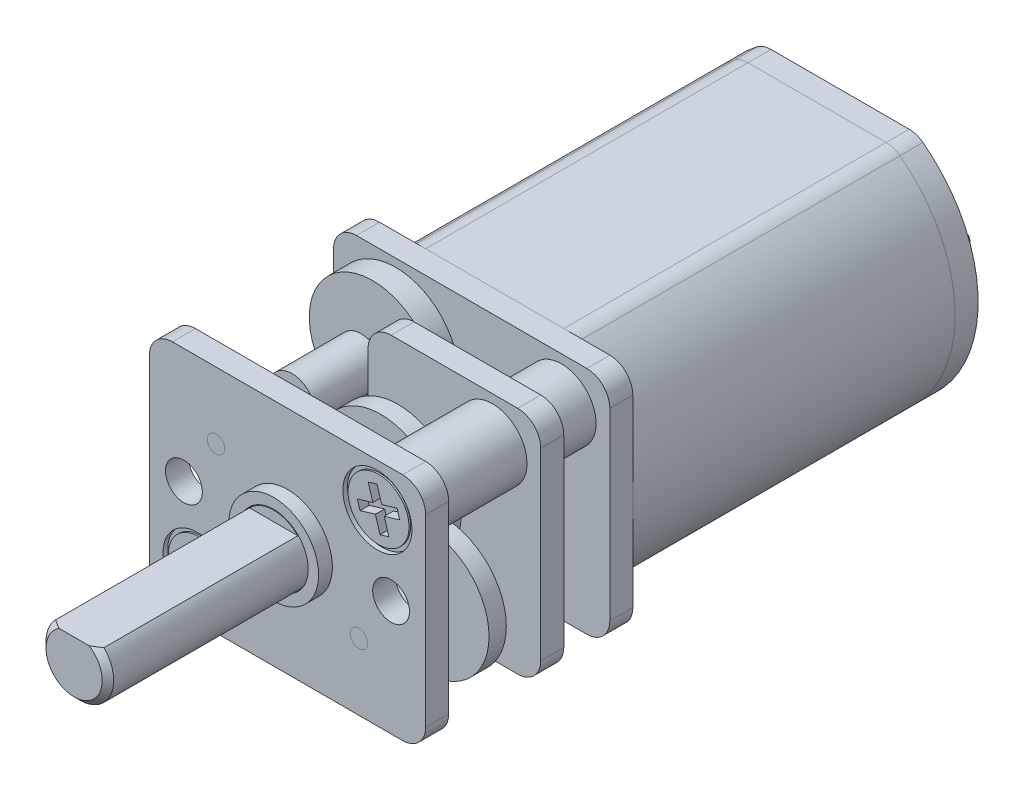
SolidWorks part; units mm, degrees
note: The reader was unsure of these and kept them because the rebuilt part matched: shared geometry of "Sketch2<2>", "Sketch9<3>", "Sketch12<2>", "Sketch29<3>".
material "Plain Carbon Steel"
ref_plane "Front Plane" through (0, 0, 0) normal (0, 0, 1) x (1, 0, 0)
ref_plane "Top Plane" through (0, 0, 0) normal (0, 1, 0) x (1, 0, 0)
ref_plane "Right Plane" through (0, 0, 0) normal (1, 0, 0) x (0, 0, -1)
sketch "Sketch1" plane through (0, 0, 0) normal (0, 0, 1) x (1, 0, 0)
  line L0 (3.3166, 5) -> (-3.3166, 5)
  line L1 (-3.3166, -5) -> (3.3166, -5)
  arc A0 (3.3166, -5) -> (3.3166, 5) centre (0, 0) ccw
  arc A1 (-3.3166, 5) -> (-3.3166, -5) centre (0, 0) ccw
  dimension "D1" = 12
  dimension "D2" = 10
extrude "Boss-Extrude1" add sketch "Sketch1" along normal mid plane 15
fillet "Fillet3" radius 1 4 edges at (-3.3166, -5, 0) (3.3166, -5, 0) (3.3166, 5, 0) (-3.3166, 5, 0)
sketch "Sketch2" plane through (0, 0, 7.5) normal (0, 0, 1) x (1, 0, 0)
  line L1 (-5, -5) -> (5, -5)
  line L2 (-6, -4) -> (-6, 4)
  line L3 (-5, 5) -> (5, 5)
  line L4 (6, -4) -> (6, 4)
  line L5 (-6, -5) -> (6, 5) construction
  line L6 (-6, 5) -> (6, -5) construction
  arc A0 (-5, -5) -> (-6, -4) centre (-5, -4) cw
  arc A1 (5, -5) -> (6, -4) centre (5, -4) ccw
  arc A2 (5, 5) -> (6, 4) centre (5, 4) cw
  arc A3 (-6, 4) -> (-5, 5) centre (-5, 4) cw
  point P0 (0, 0)
  dimension "D3" = 1
  dimension "D1" = 12
  dimension "D2" = 10
extrude "Boss-Extrude2" add sketch "Sketch2" along normal blind 1 separate body
extrude "Boss-Extrude3" add sketch "Sketch2<2>" against normal blind 1 from offset 9 separate body
sketch "Sketch2<2>" plane through (0, 0, 7.5) normal (0, 0, 1) x (1, 0, 0) same geometry as "Sketch2"
sketch "Sketch7" plane through (0, 0, 8.5) normal (0, 0, 1) x (1, 0, 0)
  line L0 (-3.1041, 2.1041) -> (3.1041, -2.1041) construction
  line L1 (0, 0) -> (0, 50000) construction
  line L2 (-6, 4) -> (-6, -4) construction
  line L3 (5, 5) -> (-5, 5) construction
  circle A0 centre (0, 0) radius 3.75 construction
  circle A1 centre (-3.1041, 2.1041) radius 0.5
  circle A2 centre (3.1041, -2.1041) radius 0.5
  circle A3 centre (-3.1041, 2.1041) radius 2.8959 construction
  point P3 (3.1041, -2.1041)
  point P4 (-3.1041, 2.1041)
  dimension "D1" = 7.5
  dimension "D3" = 1
extrude "Boss-Extrude5" add sketch "Sketch7" along normal up to surface (8 mm away) separate body up to face at (0, 0, 16.5)
sketch "Sketch11" plane through (0, 0, 8.5) normal (0, 0, 1) x (1, 0, 0)
  line L0 (-5, -1.25) -> (-2.5, -1.25)
  line L1 (-1.5, -0.25) -> (-1.5, 4)
  line L4 (-5, -5) -> (5, -5)
  line L5 (6, -4) -> (6, 4)
  line L6 (5, 5) -> (-5, 5)
  line L7 (-6, 4) -> (-6, -4)
  line L8 (-5, -5) -> (5, -5)
  line L9 (6, -4) -> (6, 4)
  line L10 (5, 5) -> (-0.5, 5)
  line L11 (-6, -2.25) -> (-6, -4)
  arc A0 (-1.5, 4) -> (-0.5, 5) centre (-0.5, 4) cw
  arc A1 (-2.5, -1.25) -> (-1.5, -0.25) centre (-2.5, -0.25) ccw
  arc A2 (-5, -1.25) -> (-6, -2.25) centre (-5, -2.25) ccw
  arc A4 (-6, -4) -> (-5, -5) centre (-5, -4) ccw
  arc A5 (5, -5) -> (6, -4) centre (5, -4) ccw
  arc A6 (6, 4) -> (5, 5) centre (5, 4) ccw
  arc A7 (-5, 5) -> (-6, 4) centre (-5, 4) ccw
  arc A8 (-6, -4) -> (-5, -5) centre (-5, -4) ccw
  arc A9 (5, -5) -> (6, -4) centre (5, -4) ccw
  arc A10 (6, 4) -> (5, 5) centre (5, 4) ccw
  dimension "D2" = 1
  dimension "D3" = 7.5
  dimension "D4" = 3.75
  dimension "D1" = 0
extrude "Boss-Extrude8" add sketch "Sketch11" along normal blind 1 from offset 2 separate body
sketch "Sketch5" plane through (0, 0, 16.5) normal (0, 0, 1) x (1, 0, 0)
  line L0 (5, 4) -> (-5, -4) construction
  circle A0 centre (0, 0) radius 0.75
  circle A1 centre (-3.1041, 2.1041) radius 0.38
  circle A2 centre (3.1041, -2.1041) radius 0.38
  circle A3 centre (0, 0) radius 5 construction
  circle A4 centre (3.9043, 3.1235) radius 0.75
  circle A5 centre (-3.9043, -3.1235) radius 0.75
  circle A6 centre (0, 0) radius 5.75 construction
  dimension "D1" = 1.5
  dimension "D2" = 0.76
  dimension "D3" = 11.5
  dimension "D4" = 1.5
extrude "Cut-Extrude1" cut sketch "Sketch5" against normal up to surface (9 mm away)
sketch "Sketch8" plane through (0, 0, 16.5) normal (0, 0, 1) x (1, 0, 0)
  circle A0 centre (-3.1041, 2.1041) radius 0.5
  circle A1 centre (3.1041, -2.1041) radius 0.5
  circle A2 centre (-3.1041, 2.1041) radius 0.5 construction
  circle A3 centre (-3.1041, 2.1041) radius 0.38
  circle A4 centre (3.1041, -2.1041) radius 0.38
  circle A5 centre (-3.1041, 2.1041) radius 0.38 construction
extrude "Cut-Extrude2" cut sketch "Sketch8" against normal blind 1
sketch "Sketch9" plane through (0, 0, 8.5) normal (0, 0, 1) x (1, 0, 0)
  circle A0 centre (-3.1041, 2.1041) radius 2.75
  circle A1 centre (-3.1041, 2.1041) radius 0.5
  circle A2 centre (-3.1041, 2.1041) radius 0.5 construction
  circle A3 centre (0, 0) radius 1
  circle M1 centre (0, 0) radius 0.75
  dimension "D1" = 5.5
  dimension "D2" = 2
extrude "Boss-Extrude6" add sketch "Sketch9" along normal blind 1 from offset 0.2 separate body contours A0 A1
extrude "Boss-Extrude16" add sketch "Sketch9<3>" along normal blind 1.3 from offset 0.1 separate body contours A3 M1 | M1
sketch "Sketch9<3>" plane through (0, 0, 8.5) normal (0, 0, 1) x (1, 0, 0) same geometry as "Sketch9"
sketch "Sketch6" plane through (0, 0, 16.5) normal (0, 0, 1) x (1, 0, 0)
  circle A0 centre (0, 0) radius 1.95
  circle A1 centre (0, 0) radius 0.75
  circle A2 centre (0, 0) radius 0.75 construction
  dimension "D1" = 3.9
extrude "Boss-Extrude4" add sketch "Sketch6" along normal blind 0.6
sketch "Sketch10" plane through (0, 0, 9.7) normal (0, 0, 1) x (1, 0, 0)
  circle A0 centre (-3.1041, 2.1041) radius 0.5
  circle A1 centre (-3.1041, 2.1041) radius 1
  circle A2 centre (0, 0) radius 2.75 construction
  circle A4 centre (-3.1041, 2.1041) radius 0.5 construction
  circle A5 centre (-3.1041, 2.1041) radius 2.75 construction
extrude "Boss-Extrude7" add sketch "Sketch10" along normal blind 3 from offset 0.5 separate body
sketch "Sketch12" plane through (0, 0, 8.5) normal (0, 0, 1) x (1, 0, 0)
  circle A0 centre (-3.9043, -3.1235) radius 0.75
  circle A1 centre (-3.9043, -3.1235) radius 1.5
  circle A2 centre (-3.9043, -3.1235) radius 0.75 construction
  circle A3 centre (3.9043, 3.1235) radius 0.75
  circle A4 centre (3.9043, 3.1235) radius 1.5
  dimension "D1" = 3
extrude "Boss-Extrude9" add sketch "Sketch12" along normal up to next (2 mm away) separate body
extrude "Boss-Extrude10" add sketch "Sketch12<2>" along normal up to next (7 mm away) from surface at 3 separate body starting at face at (0.75, 0, 11.5)
sketch "Sketch12<2>" plane through (0, 0, 8.5) normal (0, 0, 1) x (1, 0, 0) same geometry as "Sketch12"
sketch "Sketch13" plane through (0, 0, 17.1) normal (0, 0, 1) x (1, 0, 0)
  circle A0 centre (0, 0) radius 1.5
  dimension "D1" = 3
extrude "Cut-Extrude3" cut sketch "Sketch13" against normal up to next (7.2 mm away)
sketch "Sketch14" plane through (0, 0, 16.5) normal (0, 0, 1) x (1, 0, 0)
  circle A0 centre (3.9043, 3.1235) radius 1.5
  circle A1 centre (-3.9043, -3.1235) radius 1.5
  dimension "D1" = 3
extrude "Cut-Extrude4" cut sketch "Sketch14" against normal blind 0.2
chamfer "Chamfer1" distance 0.5 angle 45 2 edges at (-3.1543, -3.1235, 16.3) (4.6543, 3.1235, 16.3)
sketch "Sketch15" plane through (0, 0, 11.5) normal (0, 0, 1) x (1, 0, 0)
  circle A0 centre (0, 0) radius 2.75
  circle A1 centre (-3.1041, 2.1041) radius 1 construction
extrude "Boss-Extrude11" add sketch "Sketch15" along normal blind 0.75 from offset 0.2 separate body
sketch "Sketch16" plane through (0, 0, 12.45) normal (0, 0, 1) x (1, 0, 0)
  circle A0 centre (0, 0) radius 1
  circle A2 centre (0, 0) radius 1 construction
extrude "Boss-Extrude12" add sketch "Sketch16" along normal blind 1.15 from offset 0.2
sketch "Sketch17" plane through (0, 0, 12.45) normal (0, 0, 1) x (1, 0, 0)
  circle A0 centre (3.1041, -2.1041) radius 2.75
  circle A2 centre (0, 0) radius 1 construction
extrude "Boss-Extrude13" add sketch "Sketch17" along normal blind 0.75 from offset 0.4 separate body
sketch "Sketch18" plane through (0, 0, 13.6) normal (0, 0, 1) x (1, 0, 0)
  circle A0 centre (3.1041, -2.1041) radius 1
  circle A1 centre (0, 0) radius 1 construction
extrude "Boss-Extrude14" add sketch "Sketch18" along normal blind 1.5 from offset 0.2
sketch "Sketch19" plane through (0, 0, 15.3) normal (0, 0, 1) x (1, 0, 0)
  circle A0 centre (3.1041, -2.1041) radius 0.5
  circle A1 centre (3.1041, -2.1041) radius 0.5 construction
extrude "Cut-Extrude5" cut sketch "Sketch19" against normal through all
sketch "Sketch20" plane through (0, 0, 15.3) normal (0, 0, 1) x (1, 0, 0)
  circle A0 centre (0, 0) radius 2.75
  circle A1 centre (3.1041, -2.1041) radius 1 construction
extrude "Boss-Extrude15" add sketch "Sketch20" against normal blind 1 separate body
sketch "Sketch21" plane through (0, 0, 15.3) normal (0, 0, 1) x (1, 0, 0)
  circle A0 centre (0, 0) radius 0.5
  dimension "D1" = 1
extrude "Cut-Extrude6" cut sketch "Sketch21" against normal up to surface (7.8 mm away)
sketch "Sketch22" plane through (0, 0, 0) normal (0, 1, 0) x (1, 0, 0)
  line L0 (0, 0) -> (0, -50000) construction
  line L1 (-3, 7.5) -> (3, 7.5) construction
  line L2 (-0.5, -7.5) -> (-0.5, -15.3)
  line L3 (0.75, -7.5) -> (-0.75, -7.5) construction
  line L4 (-0.5, -15.3) -> (0.5, -15.3) construction
  line L5 (-0.5, -15.3) -> (-1.47, -15.3)
  line L6 (-2.75, -15.3) -> (2.75, -15.3) construction
  line L7 (-1.47, -15.3) -> (-1.47, -25.77)
  line L8 (-1.47, -25.77) -> (0, -25.77)
  line L9 (0, -25.77) -> (0, -7.5)
  line L10 (3, -7.5) -> (-3, -7.5) construction
  line L11 (0, -7.5) -> (-0.5, -7.5)
  line L12 (5, -16.5) -> (-5, -16.5) construction
  point P4 (0, 7.5)
  dimension "D1" = 1
  dimension "D2" = 2.94
  dimension "D3" = 9.27
revolve "Revolve1" add sketch "Sketch22" angle 360 about L0
chamfer "Chamfer2" distance 0.25 angle 45 1 edges at (-1.47, 0, 25.77)
sketch "Sketch23" plane through (0, 0, 25.77) normal (0, 0, 1) x (1, 0, 0)
  line L0 (1.0488, 1.03) -> (-1.0488, 1.03)
  circle A0 centre (0, 0) radius 1.47 construction
  arc A1 (1.0488, 1.03) -> (-1.0488, 1.03) centre (0, 0) ccw
  point P4 (0, -1.47)
  dimension "D1" = 2.5
extrude "Cut-Extrude7" cut sketch "Sketch23" against normal up to surface (8.67 mm away) up to face at (1.5, 0, 17.1)
sketch "Sketch24" plane through (0, 0, 16.5) normal (0, 0, 1) x (1, 0, 0)
  circle A0 centre (4.5, 0) radius 0.8
  circle A1 centre (-4.5, 0) radius 0.8
  dimension "D3" = 1.6
  dimension "D1" = 4.5
  dimension "D2" = 9
extrude "Cut-Extrude8" cut sketch "Sketch24" against normal up to next (1 mm away)
sketch "Sketch25" plane through (0, 0, -7.5) normal (0, 0, -1) x (-1, 0, 0)
  line L2 (-3, -5) -> (3, -5)
  line L3 (3, 5) -> (-3, 5)
  line L4 (-3, -5) -> (3, -5)
  line L5 (3, 5) -> (-3, 5)
  arc A2 (-3.6, 4.8) -> (-3.6, -4.8) centre (0, 0) ccw
  arc A3 (3.6, -4.8) -> (3.6, 4.8) centre (0, 0) ccw
  arc A4 (-3.6, 4.8) -> (-3.6, -4.8) centre (0, 0) ccw
  arc A5 (3.6, -4.8) -> (3.6, 4.8) centre (0, 0) ccw
  arc A10 (3, -5) -> (3.6, -4.8) centre (3, -4) ccw
  arc A11 (3, -5) -> (3.6, -4.8) centre (3, -4) ccw
  arc A12 (3.6, 4.8) -> (3, 5) centre (3, 4) ccw
  arc A13 (3.6, 4.8) -> (3, 5) centre (3, 4) ccw
  arc A14 (-3, 5) -> (-3.6, 4.8) centre (-3, 4) ccw
  arc A15 (-3, 5) -> (-3.6, 4.8) centre (-3, 4) ccw
  arc A16 (-3.6, -4.8) -> (-3, -5) centre (-3, -4) ccw
  arc A17 (-3.6, -4.8) -> (-3, -5) centre (-3, -4) ccw
  dimension "D1" = 0
extrude "Cut-Extrude9" cut sketch "Sketch25" against normal blind 1
sketch "Sketch26" plane through (0, 0, -6.5) normal (0, 0, -1) x (-1, 0, 0)
  line L2 (-3, -5) -> (3, -5)
  line L3 (3, 5) -> (-3, 5)
  line L4 (-3, -5) -> (3, -5)
  line L5 (3, 5) -> (-3, 5)
  arc A2 (-3.6, 4.8) -> (-3.6, -4.8) centre (0, 0) ccw
  arc A3 (3.6, -4.8) -> (3.6, 4.8) centre (0, 0) ccw
  arc A4 (-3.6, 4.8) -> (-3.6, -4.8) centre (0, 0) ccw
  arc A5 (3.6, -4.8) -> (3.6, 4.8) centre (0, 0) ccw
  arc A10 (-3.6, -4.8) -> (-3, -5) centre (-3, -4) ccw
  arc A11 (-3.6, -4.8) -> (-3, -5) centre (-3, -4) ccw
  arc A12 (3, -5) -> (3.6, -4.8) centre (3, -4) ccw
  arc A13 (3, -5) -> (3.6, -4.8) centre (3, -4) ccw
  arc A14 (3.6, 4.8) -> (3, 5) centre (3, 4) ccw
  arc A15 (3.6, 4.8) -> (3, 5) centre (3, 4) ccw
  arc A16 (-3, 5) -> (-3.6, 4.8) centre (-3, 4) ccw
  arc A17 (-3, 5) -> (-3.6, 4.8) centre (-3, 4) ccw
  dimension "D1" = 0
extrude "Boss-Extrude17" add sketch "Sketch26" along normal blind 1 separate body
sketch "Sketch27" plane through (0, 0, -7.5) normal (0, 0, -1) x (-1, 0, 0)
  circle A0 centre (0, 0) radius 2.5
  dimension "D1" = 5
extrude "Boss-Extrude18" add sketch "Sketch27" along normal blind 1.5
sketch "Sketch28" plane through (0, 0, -7.5) normal (0, 0, -1) x (-1, 0, 0)
  line L1 (3.35, 0.75) -> (3.65, 0.75)
  line L2 (3.35, 0.75) -> (3.35, -0.75)
  line L3 (3.35, -0.75) -> (3.65, -0.75)
  line L4 (3.65, 0.75) -> (3.65, -0.75)
  line L5 (3.35, 0.75) -> (3.65, -0.75) construction
  line L6 (3.35, -0.75) -> (3.65, 0.75) construction
  line L7 (-3.65, 0.75) -> (-3.35, 0.75)
  line L8 (-3.65, 0.75) -> (-3.65, -0.75)
  line L9 (-3.65, -0.75) -> (-3.35, -0.75)
  line L10 (-3.35, 0.75) -> (-3.35, -0.75)
  line L11 (-3.65, 0.75) -> (-3.35, -0.75) construction
  line L12 (-3.65, -0.75) -> (-3.35, 0.75) construction
  point P0 (3.5, 0)
  point P5 (-3.5, 0)
  dimension "D1" = 3.5
  dimension "D2" = 7
  dimension "D3" = 0.3
  dimension "D4" = 1.5
extrude "Boss-Extrude19" add sketch "Sketch28" along normal blind 2 separate body
fillet "Fillet1" radius 0.7 2 edges at (-3.5, -0.75, -9.5) (-3.5, 0.75, -9.5)
fillet "Fillet2" radius 0.7 2 edges at (3.5, -0.75, -9.5) (3.5, 0.75, -9.5)
ref_plane "Plane1" through (0, 0, 0) normal (0.6247, -0.7809, 0) x (0.7809, 0.6247, 0)
sketch "Sketch29" plane through (0, 0, 0) normal (0.6247, -0.7809, 0) x (0.7809, 0.6247, 0)
  line L0 (5, 16.5) -> (5, 50016.5) construction
  line L1 (6.5, 16.5) -> (3.5, 16.5) construction
  line L2 (-5, 16.5) -> (-5, 50016.5) construction
  line L3 (-3.5, 16.5) -> (-6.5, 16.5) construction
  line L4 (5.7, 7.5) -> (5.7, 15.755)
  line L5 (6, 7.5) -> (-0.1874, 7.5) construction
  line L6 (5.7, 15.755) -> (6.325, 16.38)
  line L7 (6.325, 16.38) -> (6.325, 16.45)
  line L8 (6.325, 16.45) -> (5, 16.45)
  line L9 (5, 16.45) -> (5, 7.5)
  line L10 (4.25, 7.5) -> (5.75, 7.5) construction
  line L11 (5, 7.5) -> (5.7, 7.5)
  line L12 (2.1864, 16.5) -> (7.184, 16.5) construction
  line L13 (0, 0) -> (0, 50000) construction
  line L14 (-5, 7.5) -> (-5.7, 7.5)
  line L15 (-5, 16.45) -> (-5, 7.5)
  line L16 (-6.325, 16.45) -> (-5, 16.45)
  line L17 (-6.325, 16.38) -> (-6.325, 16.45)
  line L18 (-5.7, 15.755) -> (-6.325, 16.38)
  line L19 (-5.7, 7.5) -> (-5.7, 15.755)
  point P4 (5, 16.5)
  point P9 (-5, 16.5)
  dimension "D1" = 45
  dimension "D2" = 1.4
  dimension "D3" = 2.65
  dimension "D4" = 0.05
  dimension "D5" = 0.07
revolve "Revolve2" add sketch "Sketch29" angle 360 about L0
revolve "Revolve3" add sketch "Sketch29<3>" angle 360 about L2
sketch "Sketch29<3>" plane through (0, 0, 0) normal (0.6247, -0.7809, 0) x (0.7809, 0.6247, 0) same geometry as "Sketch29"
sketch "Sketch30" plane through (0, 0, 16.45) normal (0, 0, 1) x (1, 0, 0)
  line L0 (-3.5871, -2.2813) -> (-4.2216, -3.9657) construction
  line L1 (-3.7742, -2.2107) -> (-4.021, -2.8658)
  line L2 (-4.7466, -2.8062) -> (-3.0621, -3.4408) construction
  line L3 (-4.8171, -2.9934) -> (-4.162, -3.2401)
  line L4 (-3.3999, -2.3518) -> (-3.6467, -3.0068)
  line L5 (-4.6761, -2.619) -> (-4.021, -2.8658)
  line L6 (-3.7742, -2.2107) -> (-3.3999, -2.3518)
  line L7 (-4.4088, -3.8952) -> (-4.0345, -4.0362)
  line L8 (-4.8171, -2.9934) -> (-4.6761, -2.619)
  line L9 (-3.1326, -3.6279) -> (-2.9916, -3.2536)
  line L10 (-4.162, -3.2401) -> (-4.4088, -3.8952)
  line L11 (-3.7742, -2.2107) -> (-4.4088, -3.8952) construction
  line L12 (-3.6467, -3.0068) -> (-2.9916, -3.2536)
  line L13 (-4.6761, -2.619) -> (-2.9916, -3.2536) construction
  line L14 (-3.7877, -3.3811) -> (-4.0345, -4.0362)
  line L15 (-3.3999, -2.3518) -> (-4.0345, -4.0362) construction
  line L16 (-3.7877, -3.3811) -> (-3.1326, -3.6279)
  line L17 (-4.8171, -2.9934) -> (-3.1326, -3.6279) construction
  line L18 (3.6482, 3.9863) -> (4.1605, 2.2607) construction
  line L19 (3.0416, 2.8674) -> (4.7671, 3.3796) construction
  line L20 (3.4565, 3.9293) -> (3.6557, 3.2583)
  line L21 (3.0985, 2.6756) -> (3.7695, 2.8748)
  line L22 (3.84, 4.0432) -> (4.0392, 3.3721)
  line L23 (2.9846, 3.0591) -> (3.6557, 3.2583)
  line L24 (3.4565, 3.9293) -> (3.84, 4.0432)
  line L25 (3.9687, 2.2038) -> (4.3522, 2.3176)
  line L26 (3.0985, 2.6756) -> (2.9846, 3.0591)
  line L27 (4.824, 3.1879) -> (4.7102, 3.5713)
  line L28 (4.0392, 3.3721) -> (4.7102, 3.5713)
  line L29 (2.9846, 3.0591) -> (4.7102, 3.5713) construction
  line L30 (3.7695, 2.8748) -> (3.9687, 2.2038)
  line L31 (3.4565, 3.9293) -> (3.9687, 2.2038) construction
  line L32 (4.153, 2.9887) -> (4.824, 3.1879)
  line L33 (3.0985, 2.6756) -> (4.824, 3.1879) construction
  line L34 (4.153, 2.9887) -> (4.3522, 2.3176)
  line L35 (3.84, 4.0432) -> (4.3522, 2.3176) construction
  point P2 (-3.9043, -3.1235)
  point P15 (3.9043, 3.1235)
  dimension "D1" = 1.8
  dimension "D2" = 0.2
  dimension "D3" = 0.2
  dimension "D4" = 0.2
  dimension "D5" = 0.2
extrude "Cut-Extrude10" cut sketch "Sketch30" against normal blind 0.4
